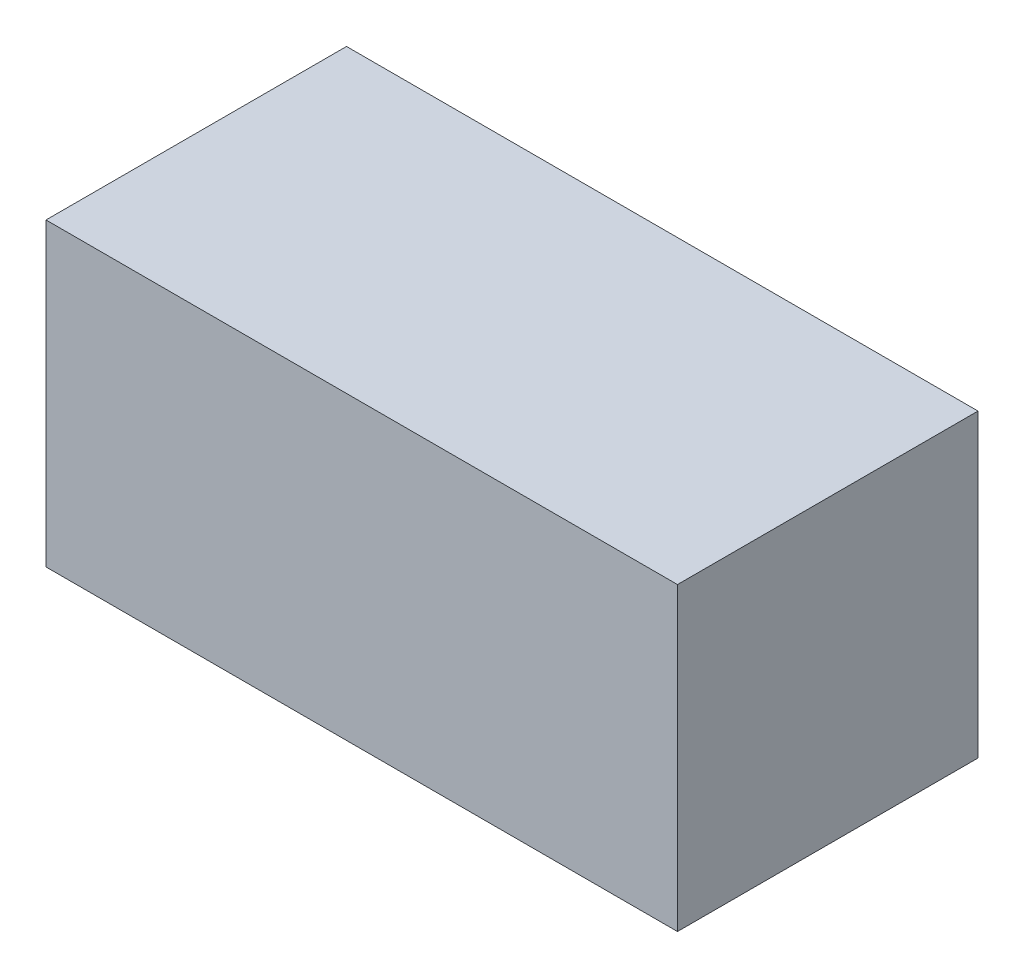
SolidWorks part; units mm, degrees
ref_plane "Front Plane" through (0, 0, 0) normal (0, 0, 1) x (1, 0, 0)
ref_plane "Top Plane" through (0, 0, 0) normal (0, 1, 0) x (1, 0, 0)
ref_plane "Right Plane" through (0, 0, 0) normal (1, 0, 0) x (0, 0, -1)
sketch "Sketch2" plane through (0, 0, 0) normal (1, 0, 0) x (0, 0, -1)
  line L0 (-2.3812, -2.3813) -> (2.3813, 2.3813) construction
  line L1 (-2.3813, 2.3813) -> (2.3813, 2.3813) construction
  line L2 (-2.3813, 2.3813) -> (-2.3812, -2.3813) construction
  line L3 (-2.3812, -2.3813) -> (2.3813, -2.3813) construction
  line L4 (2.3813, 2.3813) -> (2.3813, -2.3813) construction
  dimension "Height" = 4.7625
  dimension "Width" = 4.7625
sketch "Sketch1" plane through (0, 0, 0) normal (0, 0, 1) x (1, 0, 0)
  line L0 (-6.35, 0) -> (6.35, 0) construction
  line L1 (-6.35, 2.3813) -> (6.35, 2.3813) construction
  point P8 (0, 0)
  dimension "Length" = 12.7
sketch "Sketch3" plane through (0, 0, 0) normal (0, 1, 0) x (1, 0, 0)
  line L1 (-5.0038, 2.3813) -> (5.0038, 2.3813)
  line L2 (-5.0038, 2.3813) -> (-5.0038, -2.3812)
  line L3 (-5.0038, -2.3812) -> (5.0038, -2.3812)
  line L4 (5.0038, 2.3813) -> (5.0038, -2.3812)
  dimension "D1" = 10.0076
extrude "Extrude1" add sketch "Sketch3" against normal up to vertex (-2.3813 mm away) and the other way up to vertex (-2.3813 mm away) up to point (0, 2.3813, 2.3813) other way up to point (0, -2.3813, 2.3812)
sketch "Sketch5" plane through (0, 0, 0) normal (0, 0, 1) x (1, 0, 0)
  line L0 (6.35, 0) -> (2.1167, 0) construction
  line L1 (2.1167, 0) -> (-2.1167, 0) construction
  line L2 (-2.1167, 0) -> (2.1167, 0) construction
  line L3 (2.1167, 0) -> (-2.1167, 0) construction
  line L4 (-2.1167, 0) -> (-6.35, 0) construction
  point P2 (-4.2333, 0)
  point P7 (0, 0)
  point P8 (4.2333, 0)
  point P9 (-2.1167, 0)
  point P10 (-6.35, 0)
  point P11 (2.1167, 0)
  point P13 (6.35, 0)
sketch "Sketch6" plane through (0, 0, 2.3812) normal (0, 0, 1) x (1, 0, 0)
  line L1 (-2.1167, 0) -> (-6.35, 0) construction
  line L2 (2.1167, 0) -> (-2.1167, 0) construction
  line L3 (6.35, 0) -> (2.1167, 0) construction
  point P0 (-4.2333, 0)
  point P1 (-2.1167, 0)
  point P4 (0, 0)
  point P5 (2.1167, 0)
  point P6 (4.2333, 0)
ref_plane "Plane1" through (-4.9962, 0, 0) normal (1, 0, 0) x (0, 0, -1)
